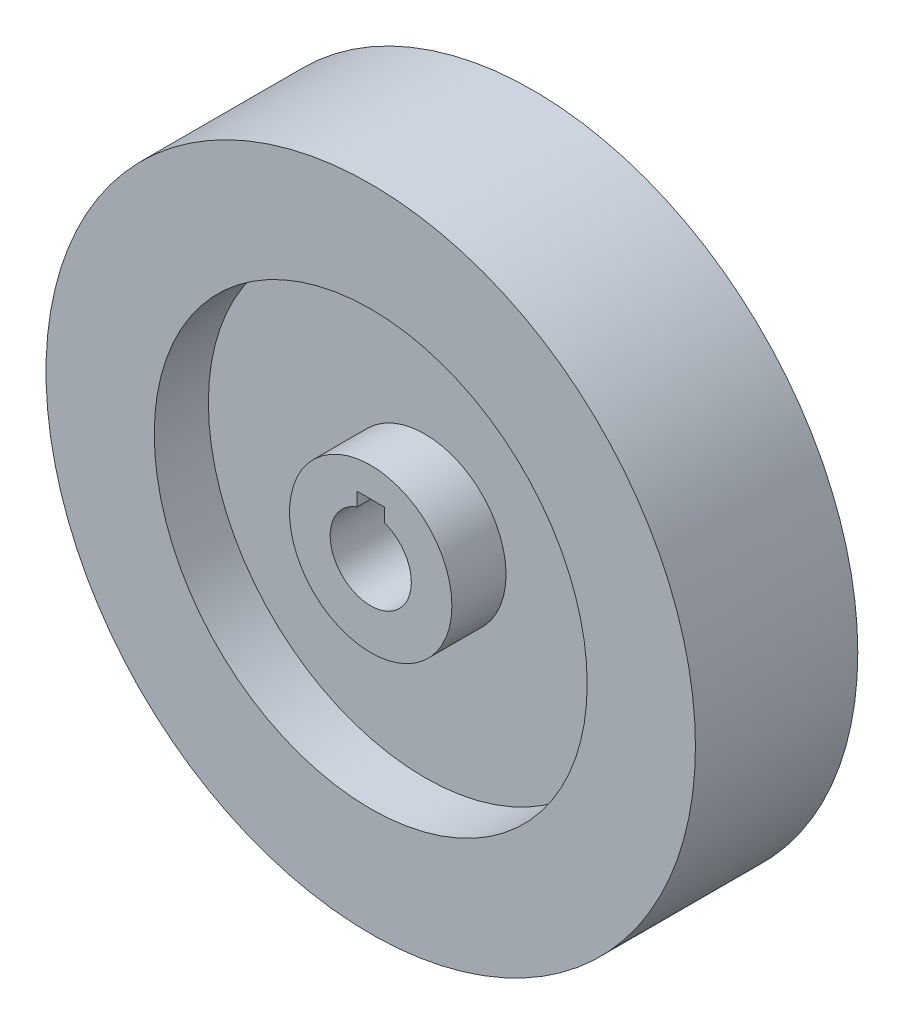
SolidWorks part; units mm, degrees
ref_plane "Front Plane" through (0, 0, 0) normal (0, 0, 1) x (1, 0, 0)
ref_plane "Top Plane" through (0, 0, 0) normal (0, 1, 0) x (1, 0, 0)
ref_plane "Right Plane" through (0, 0, 0) normal (1, 0, 0) x (0, 0, -1)
sketch "Sketch1" plane through (0, 0, 0) normal (1, 0, 0) x (0, 0, -1)
  line L0 (-34.2145, 0) -> (34.2145, 0) construction
  line L1 (0, 0) -> (0, 76.2) construction
  line L2 (19.05, 9.525) -> (-19.05, 9.525)
  line L3 (-19.05, 9.525) -> (-19.05, 19.05)
  line L4 (-19.05, 19.05) -> (-6.35, 19.05)
  line L5 (-6.35, 19.05) -> (-6.35, 50.8)
  line L6 (-6.35, 50.8) -> (-19.05, 50.8)
  line L7 (-19.05, 50.8) -> (-19.05, 76.2)
  line L8 (-19.05, 76.2) -> (19.05, 76.2)
  line L9 (19.05, 9.525) -> (19.05, 19.05)
  line L10 (19.05, 19.05) -> (6.35, 19.05)
  line L11 (6.35, 19.05) -> (6.35, 50.8)
  line L12 (6.35, 50.8) -> (19.05, 50.8)
  line L13 (19.05, 50.8) -> (19.05, 76.2)
  point P13 (0, 9.525)
  dimension "D1" = 38.1
  dimension "D2" = 152.4
  dimension "D3" = 19.05
  dimension "D4" = 12.7
  dimension "D5" = 38.1
  dimension "D6" = 25.4
revolve "Revolve1" add sketch "Sketch1" angle 360 about L0
sketch "Sketch4" plane through (0, 0, -19.05) normal (0, 0, -1) x (-1, 0, 0)
  line L0 (-3.175, 8.9803) -> (3.175, 8.9803)
  line L1 (3.175, 8.9803) -> (3.175, 12.1553)
  line L2 (3.175, 12.1553) -> (-3.175, 12.1553)
  line L3 (-3.175, 12.1553) -> (-3.175, 8.9803)
  circle A0 centre (0, 0) radius 9.525 construction
  dimension "D1" = 6.35
  dimension "D2" = 3.175
extrude "Cut-Extrude1" cut sketch "Sketch4" against normal through all
